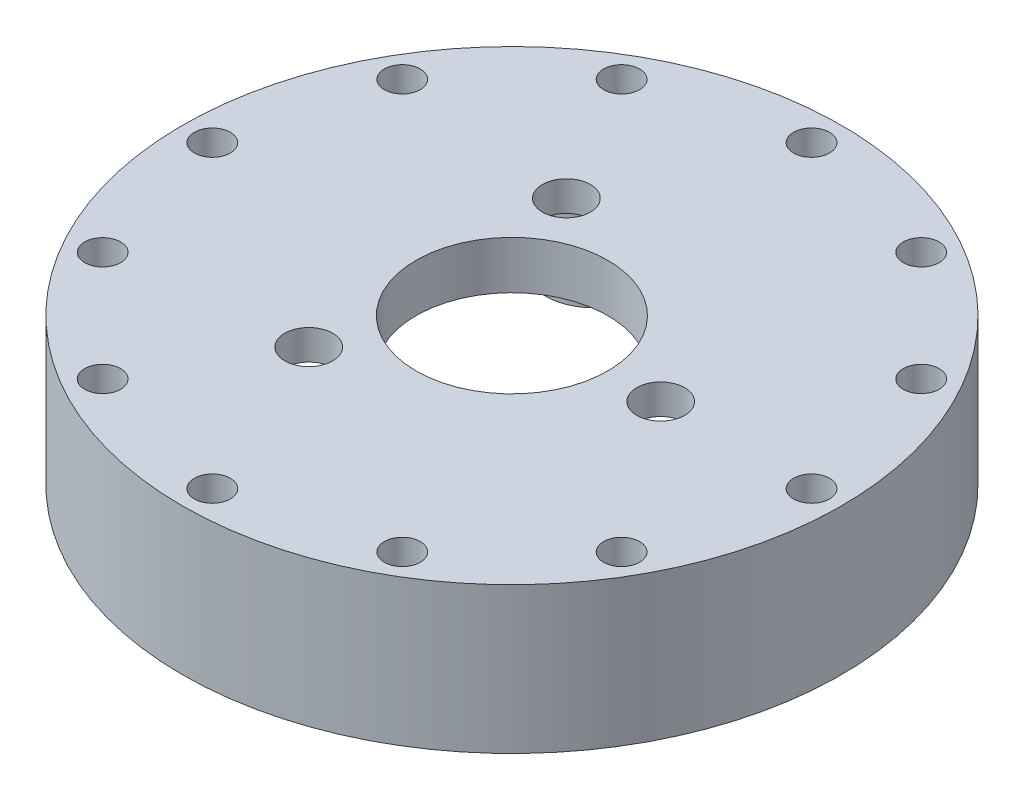
SolidWorks part; units mm, degrees
ref_plane "Front Plane" through (0, 0, 0) normal (0, 0, 1) x (1, 0, 0)
ref_plane "Top Plane" through (0, 0, 0) normal (0, 1, 0) x (1, 0, 0)
ref_plane "Right Plane" through (0, 0, 0) normal (1, 0, 0) x (0, 0, -1)
sketch "Sketch1" plane through (0, 0, 0) normal (0, 1, 0) x (1, 0, 0)
  line L0 (0, 22.5) -> (0, 0) construction
  line L1 (0, 0) -> (12.1644, 18.9282) construction
  line L2 (0, 0) -> (-12.1644, 18.9282) construction
  line L3 (-20.4667, 9.3468) -> (0, 0) construction
  line L4 (0, 0) -> (-22.271, -3.2021) construction
  circle A0 centre (0, 0) radius 22.5
  circle A1 centre (0, 0) radius 27.5
  circle A2 centre (0, 22.5) radius 3.925
  circle A3 centre (12.1644, 18.9282) radius 3.925
  circle A4 centre (20.4667, 9.3468) radius 3.925
  circle A5 centre (22.271, -3.2021) radius 3.925
  circle A6 centre (17.0044, -14.7344) radius 3.925
  circle A7 centre (6.339, -21.5886) radius 3.925
  circle A8 centre (-6.339, -21.5886) radius 3.925
  circle A9 centre (-17.0044, -14.7344) radius 3.925
  circle A10 centre (-22.271, -3.2021) radius 3.925
  circle A11 centre (-20.4667, 9.3468) radius 3.925
  circle A12 centre (-12.1644, 18.9282) radius 3.925
  point P27 (0, 0)
  dimension "D1" = 45
  dimension "D2" = 55
  dimension "D3" = 7.85
  dimension "D4" = 11
extrude "Boss-Extrude2" add sketch "Sketch1" along normal blind 8.2 contours A1 A12 A0 A2 A3 A4 A5 A6 A7 A8 A9 A10 A11 | A0 A11 | A0 A11 | A0 A12 | A0 A12 | A0 A2 | A0 A2 | A0 A3 | A0 A3 | A0 A4 | A0 A4 | A0 A5 | A0 A5 | A0 A6 | A0 A6 | A0 A7 | A0 A7 | A0 A8 | A0 A8 | A0 A9 | A0 A9 | A0 A10 | A0 A10 | A12 region at (20.5626, 0, 2.9565) region at (23.8573, 0, 3.4302) region at (18.8967, 0, -8.6299) region at (21.9245, 0, -10.0126) region at (18.2156, 0, 15.7839) region at (15.7, 0, 13.6041) region at (11.2313, 0, -17.4762) region at (13.0309, 0, -20.2764) region at (6.7905, 0, 23.1263) region at (5.8527, 0, 19.9326) region at (0, 0, -20.774) region at (0, 0, -24.1026) region at (-6.7905, 0, 23.1263) region at (-5.8527, 0, 19.9326) region at (-11.2313, 0, -17.4762) region at (-13.0309, 0, -20.2764) region at (-18.2156, 0, 15.7839) region at (-15.7, 0, 13.6041) region at (-18.8967, 0, -8.6299) region at (-21.9245, 0, -10.0126) region at (-23.8573, 0, 3.4302) region at (-20.5626, 0, 2.9565) region at (-26.7222, 0, 0)
sketch "Sketch2" plane through (0, 8.2, 0) normal (0, 1, 0) x (1, 0, 0)
  line L1 (12.413, 0) -> (-6.2065, 10.75) construction
  line L2 (-6.2065, 10.75) -> (-6.2065, -10.75) construction
  line L3 (-6.2065, -10.75) -> (12.413, 0) construction
  circle A0 centre (0, 0) radius 27.5
  circle A1 centre (0, 0) radius 8
  circle A2 centre (0, 0) radius 6.2065 construction
  circle A3 centre (-6.2065, 10.75) radius 2
  circle A4 centre (12.413, 0) radius 2
  circle A5 centre (-6.2065, -10.75) radius 2
  point P16 (0, 0)
  dimension "D1" = 16
  dimension "D2" = 55
  dimension "D4" = 4
  dimension "D3" = 21.5
  dimension "D5" = 3
extrude "Boss-Extrude3" add sketch "Sketch2" along normal blind 4
fillet "Fillet2" radius 1 22 edges at (19.3062, 4.1, 11.5552) (9.9942, 4.1, 20.1585) (2.4909, 4.1, 22.3617) (14.1851, 4.1, 17.4652) (-2.4909, 4.1, 22.3617) (-9.9942, 4.1, 20.1585) (-14.1851, 4.1, 17.4652) (-19.3062, 4.1, 11.5552) (-21.3757, 4.1, 7.0236) (-22.4886, 4.1, -0.7169) (-21.7796, 4.1, -5.6479) (-18.531, 4.1, -12.7613) (-15.2687, 4.1, -16.5263) (-8.69, 4.1, -20.7541) (-3.91, 4.1, -22.1577) (3.91, 4.1, -22.1577) (8.69, 4.1, -20.7541) (15.2687, 4.1, -16.5263) (18.531, 4.1, -12.7613) (21.7796, 4.1, -5.6479) (22.4886, 4.1, -0.7169) (21.3757, 4.1, 7.0236)
sketch "Sketch8" plane through (0, 0, 0) normal (0, -1, 0) x (1, 0, 0)
  circle A0 centre (0, 0) radius 25 construction
  circle A1 centre (0, -25) radius 1.5
  circle A2 centre (-12.5, -21.6506) radius 1.5
  circle A3 centre (-21.6506, -12.5) radius 1.5
  circle A4 centre (-25, 0) radius 1.5
  circle A5 centre (-21.6506, 12.5) radius 1.5
  circle A6 centre (-12.5, 21.6506) radius 1.5
  circle A7 centre (0, 25) radius 1.5
  circle A8 centre (12.5, 21.6506) radius 1.5
  circle A9 centre (21.6506, 12.5) radius 1.5
  circle A10 centre (25, 0) radius 1.5
  circle A11 centre (21.6506, -12.5) radius 1.5
  circle A12 centre (12.5, -21.6506) radius 1.5
  point P30 (0, 0)
  dimension "D1" = 50
  dimension "D2" = 3
  dimension "D3" = 12
extrude "Cut-Extrude1" cut sketch "Sketch8" against normal through all
sketch "Sketch9" plane through (0, 8.2, 0) normal (0, -1, 0) x (1, 0, 0)
  circle A0 centre (0, 0) radius 12.413 construction
  circle A1 centre (12.413, 0) radius 4.25
  circle A2 centre (-6.2065, -10.75) radius 4.25
  circle A3 centre (-6.2065, 10.75) radius 4.25
  point P13 (0, 0)
  dimension "D1" = 8.5
  dimension "D2" = 3
extrude "Cut-Extrude2" cut sketch "Sketch9" against normal blind 1.5
